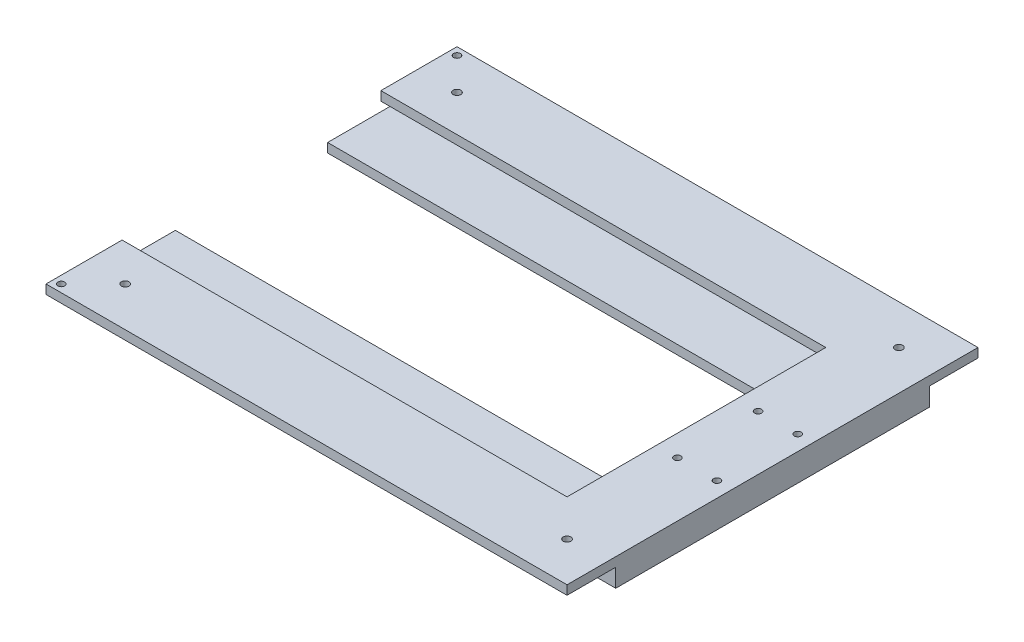
SolidWorks part; units mm, degrees
ref_plane "Спереди" through (0, 0, 0) normal (0, 0, 1) x (1, 0, 0)
ref_plane "Сверху" through (0, 0, 0) normal (0, 1, 0) x (1, 0, 0)
ref_plane "Справа" through (0, 0, 0) normal (1, 0, 0) x (0, 0, -1)
sketch "Эскиз1" plane through (0, 0, 0) normal (0, 1, 0) x (1, 0, 0)
  line L0 (50, -77.9215) -> (50, -347.9215)
  line L1 (-292.3, -77.9215) -> (50, -77.9215)
  line L2 (-292.3, -77.9215) -> (-292.3, -127.9215)
  line L3 (-292.3, -347.9215) -> (50, -347.9215)
  line L5 (-292.3, -127.9215) -> (0, -127.9215)
  line L7 (-292.3, -297.9215) -> (0, -297.9215)
  line L13 (-292.3, -297.9215) -> (-292.3, -347.9215)
  line L22 (0, -127.9215) -> (0, -297.9215)
  dimension "D1" = 342.3
  dimension "D12" = 50
  dimension "D2" = 270
  dimension "D3" = 50
  dimension "D4" = 50
  dimension "D9" = 50
  dimension "D8" = 77.9215
extrude "Бобышка-Вытянуть2" add sketch "Эскиз1" along normal blind 6
sketch "Эскиз2" plane through (0, 0, 0) normal (0, -1, 0) x (1, 0, 0)
  line L0 (-292.3, 127.9215) -> (0, 127.9215) construction
  line L5 (50, 347.9215) -> (50, 77.9215) construction
  line L6 (0, 297.9215) -> (-292.3, 297.9215) construction
  line L18 (50, 315.9215) -> (50, 109.9215)
  line L20 (6, 303.9215) -> (6, 121.9215)
  line L21 (-292.3, 77.9215) -> (-292.3, 127.9215) construction
  line L22 (50, 109.9215) -> (-292.3, 109.9215)
  line L24 (6, 121.9215) -> (-292.3, 121.9215)
  line L25 (-292.3, 109.9215) -> (-292.3, 121.9215)
  line L26 (-292.3, 297.9215) -> (-292.3, 347.9215) construction
  line L27 (50, 315.9215) -> (-292.3, 315.9215)
  line L29 (6, 303.9215) -> (-292.3, 303.9215)
  line L30 (-292.3, 315.9215) -> (-292.3, 303.9215)
  dimension "D1" = 44
  dimension "D2" = 12
  dimension "D3" = 12
  dimension "D4" = 6
  dimension "D5" = 6
extrude "Бобышка-Вытянуть3" add sketch "Эскиз2" along normal blind 6
sketch "Эскиз4" plane through (0, 6, 0) normal (0, 1, 0) x (1, 0, 0)
  line L0 (50, -77.9215) -> (-292.3, -77.9215) construction
  line L1 (-292.3, -77.9215) -> (-292.3, -127.9215) construction
  circle A0 centre (-266.3, -103.9215) radius 2.5
  dimension "D1" = 5
  dimension "D2" = 26
  dimension "D3" = 26
extrude "Вырез-Вытянуть1" cut sketch "Эскиз4" against normal through all
pattern_linear "Линейный массив2" count 2 spacing 290.3 along (1, 0, 0) count 2 spacing 218 along (0, 0, 1) of "Вырез-Вытянуть1"
sketch "Эскиз5" plane through (0, -6, 0) normal (0, -1, 0) x (1, 0, 0)
  line L8 (50, 315.9215) -> (-292.3, 315.9215)
  line L9 (-292.3, 315.9215) -> (-292.3, 262.9215)
  line L10 (-292.3, 262.9215) -> (0, 262.9215)
  line L11 (0, 262.9215) -> (0, 162.9215)
  line L12 (0, 162.9215) -> (-292.3, 162.9215)
  line L13 (-292.3, 162.9215) -> (-292.3, 109.9215)
  line L14 (-292.3, 109.9215) -> (50, 109.9215)
  line L15 (50, 109.9215) -> (50, 315.9215)
  point P0 (0, 212.9215)
  point P9 (50, 212.9215)
  dimension "D1" = 100
extrude "Бобышка-Вытянуть4" add sketch "Эскиз5" along normal blind 6
sketch "Эскиз6" plane through (0, -12, 0) normal (0, -1, 0) x (1, 0, 0)
  line L0 (40, 212.9215) -> (50, 212.9215) construction
  line L1 (40, 186.4215) -> (14, 186.4215) construction
  line L2 (40, 186.4215) -> (40, 239.4215) construction
  line L3 (40, 239.4215) -> (14, 239.4215) construction
  line L4 (14, 186.4215) -> (14, 239.4215) construction
  line L5 (50, 109.9215) -> (50, 315.9215) construction
  circle A1 centre (14, 239.4215) radius 2.25
  circle A2 centre (40, 239.4215) radius 2.25
  circle A3 centre (40, 186.4215) radius 2.25
  circle A4 centre (14, 186.4215) radius 2.25
  point P4 (50, 212.9215)
  point P6 (40, 212.9215)
  dimension "D4" = 4.5
  dimension "D1" = 53
  dimension "D2" = 26
  dimension "D3" = 10
extrude "Вырез-Вытянуть2" cut sketch "Эскиз6" against normal through all
sketch "Эскиз7" plane through (0, 0, 0) normal (0, -1, 0) x (1, 0, 0)
  line L0 (-292.3, 337.9215) -> (-282.3, 347.9215) construction
  line L1 (-292.3, 347.9215) -> (-282.3, 347.9215) construction
  line L2 (-292.3, 347.9215) -> (-292.3, 337.9215) construction
  line L3 (-292.3, 337.9215) -> (-282.3, 337.9215) construction
  line L4 (-282.3, 347.9215) -> (-282.3, 337.9215) construction
  line L5 (-292.3, 347.9215) -> (-282.3, 337.9215) construction
  line L6 (-282.3, 87.9215) -> (-292.3, 77.9215) construction
  line L7 (-292.3, 77.9215) -> (-282.3, 77.9215) construction
  line L8 (-292.3, 77.9215) -> (-292.3, 87.9215) construction
  line L9 (-292.3, 87.9215) -> (-282.3, 87.9215) construction
  line L10 (-282.3, 77.9215) -> (-282.3, 87.9215) construction
  line L11 (-292.3, 87.9215) -> (-282.3, 77.9215) construction
  circle A0 centre (-287.3, 342.9215) radius 2.25
  circle A1 centre (-287.3, 82.9215) radius 2.25
  point P12 (-287.3, 82.9215)
  dimension "D3" = 4.5
  dimension "D6" = 4.5
  dimension "D1" = 10
  dimension "D2" = 10
  dimension "D4" = 10
  dimension "D5" = 10
extrude "Вырез-Вытянуть3" cut sketch "Эскиз7" against normal through all
equation "\"Ширина груза\"= 160"
equation "\"Глубина груза\"= 240"
equation "\"Высота груза\"= 160"
equation "\"Ширина ячейки\"= \"Ширина груза\" + 10"
equation "\"Глубина ячейки\"= \"Глубина груза\" + 10"
equation "\"Высота ячейки\"= \"Высота груза\" + 10 + 13"
equation "\"Колво ячеек ширина\"= 2"
equation "\"Колво ячеек высота\"= 2"
equation "\"Толщина стенки\"= \"Толщина тонких панелей\""
equation "\"Крепление дверцы\"= 5 "
equation "\"Ширина рейки\"= \"Толщина шестерни\""
equation "\"Высота рейки\"= 20"
equation "\"Высота пола\"= 2*\"Толщина тонких панелей\""
equation "\"Колво полозьев\"= 5"
equation "\"Отступ рейки\"= 20"
equation "\"Глубина каретки\" = \"Глубина ячейки\" + 30 + \"D3@Линейный массив2\" + 20"
equation "\"Длинна рейки\"= (\"Ширина ячейки\"+\"Толщина вертикальных стенок\"+\"Крепление дверцы\")*\"Колво ячеек ширина\"+\"Ширина ячейки выгрузки\"*\"Колво выгрузки\"+\"Толщина вертикальных стенок\"+2*\"Отступ крепления мотора фиксации\"-\"Крепление дверцы\"*\"Колво ячеек ширина\""
equation "\"Отступ шпильки\"= 26"
equation "\"Диаметр шпильки\"= 5"
equation "\"Длинна шпильки\"= (\"Высота ячейки\"+\"Толщина горизонтальных плит\"+\"Высота пола\")*\"Колво ячеек высота\"+2*(\"Толщина горизонтальных плит\"+\"Отступ рейки\")"
equation "\"D2@Эскиз1\"=\"Ширина ячейки\" + \"Ширина пластины\" * 2 "
equation "\"D9@Эскиз1\"=\"Ширина пластины\""
equation "\"D3@Эскиз1\"=\"Ширина пластины\""
equation "\"D4@Эскиз1\"= \"Ширина пластины\""
equation "\"Ширина пластины\"= 50  "
equation "\"D1@Бобышка-Вытянуть2\"=\"Толщина стенки\""
equation "\"D1@Эскиз4\"= \"Диаметр шпильки\""
equation "\"D4@Линейный массив2\"=\"Ширина ячейки\" + \"Ширина пластины\" * 2  - \"Отступ шпильки\" * 2"
equation "\"D1@Эскиз1\"= \"Глубина каретки\""
equation "\"D3@Линейный массив2\"= \"Глубина каретки\" - \"Отступ шпильки\" * 2"
equation "\"D2@Эскиз4\"=\"Отступ шпильки\""
equation "\"D3@Эскиз4\"= \"Отступ шпильки\""
equation "\"D1@Эскиз2\"= \"Ширина пластины\" - \"Толщина стенки\""
equation "\"D2@Эскиз2\"=12"
equation "\"D4@Эскиз2\"= \"Толщина стенки\""
equation "\"D5@Эскиз2\"= \"Толщина стенки\""
equation "\"D1@Бобышка-Вытянуть4\"= \"Толщина стенки\""
equation "\"Вы\"=20"
equation "\"D1@Бобышка-Вытянуть3\"=6"
equation "\"Высота зона выгрузки\"= \"Высота ячейки\" * 2 + \"Толщина стенки\" * 2"
equation "\"Колво выгрузки\"= 1"
equation "\"Ширина ячейки выгрузки\"= \"Ширина ячейки\"+\"Толщина вертикальных стенок\"+2*\"Отступ крепления мотора фиксации\""
equation "\"Отступ крепления мотора фиксации\"= (\"Ширина пластины\"+20-\"Толщина вертикальных стенок\")/2"
equation "\"Мотор X ширина корпуса\"= 42.3"
equation "\"Мотор X высота корпуса\"= 42.3"
equation "\"D1@Эскиз4\" = 40"
equation "\"D4@Линейный массив2\" = 19.8"
equation "\"D1@Эскиз1\" = 42.3"
equation "\"D3@Линейный массив2\" = 42.3"
equation "\"D2@Эскиз4\" = 48"
equation "\"D3@Эскиз4\" = 30"
equation "\"D1@Эскиз2\" = 42"
equation "\"D2@Эскиз2\" = 42"
equation "\"Мотор Z длина корпуса\"= 40"
equation "\"D4@Эскиз2\" = 23"
equation "\"D5@Эскиз2\" = 5"
equation "\"D1@Бобышка-Вытянуть4\" = 31"
equation "\"Вы\" = 3"
equation "\"D1@Бобышка-Вытянуть3\" = 4.5"
equation "\"Мотор диаметр буртика ПРЕДВ\"= 22"
equation "\"Колво выгрузки\" = 2"
equation "\"Ширина ячейки выгрузки\" = 16"
equation "\"Отступ крепления мотора фиксации\" = 12"
equation "\"Мотор X ширина корпуса\" = 5"
equation "\"Мотор X высота корпуса\" = 1.8"
equation "\"Мотор X ток А\"= 1.5"
equation "\"D4@Линейный массив2\" = 1.3"
equation "\"D1@Эскиз1\" = 2"
equation "\"D3@Линейный массив2\" = 1.8"
equation "\"D2@Эскиз4\" = 2.2"
equation "\"D3@Эскиз4\" = 0.9"
equation "\"D1@Эскиз2\" = 2"
equation "\"D2@Эскиз2\" = 1.8"
equation "\"Мотор Z длина корпуса\" = 1"
equation "\"D4@Эскиз2\" = 4"
equation "\"D5@Эскиз2\" = 8"
equation "\"Мотор Y диаметр ротора\"= 25.78"
equation "\"Толщина тонких панелей\"= 6"
equation "\"Толщина вертикальных стенок\"= 6"
equation "\"Толщина горизонтальных плит\"= 6"
equation "\"Базовая высота корпуса\" =  ( \"Высота ячейки\" + \"Толщина тонких панелей\" + \"Высота пола\" )  * \"Колво ячеек высота\" + 6 * \"Толщина тонких панелей\" + \"Мотор X ширина корпуса\" + \"D1@Эскиз1\" + 75"
equation "\"Высота корпуса\" =  ( \"Высота ячейки\" + \"Толщина горизонтальных плит\" + \"Высота пола\" )  * \"Колво ячеек высота\" + 2 * \"Толщина горизонтальных плит\" + 4 * \"Толщина тонких панелей\" + \"Мотор X ширина корпуса\" + \"D1@Эскиз1\" + 75"
equation "\"Смещение центра корпуса\"= (\"Высота корпуса\"-\"Базовая высота корпуса\")/2-(\"Толщина горизонтальных плит\"-\"Толщина тонких панелей\")"
equation "\"Отметка пола\"= -\"Базовая высота корпуса\"/2+\"Толщина тонких панелей\""
equation "\"Отметка потолка\"= \"Отметка пола\"+\"Высота корпуса\"-2*\"Толщина горизонтальных плит\""
equation "\"Отметка верхней полки\"= \"Отметка потолка\"-(28+\"Толщина тонких панелей\")-\"Высота ячейки\"-\"Высота пола\""
equation "\"Отметка нижней полки\"= \"Отметка верхней полки\"-\"Высота ячейки\"-\"Высота пола\"-\"Толщина горизонтальных плит\""
equation "\"Толщина шестерни\"= 10"
